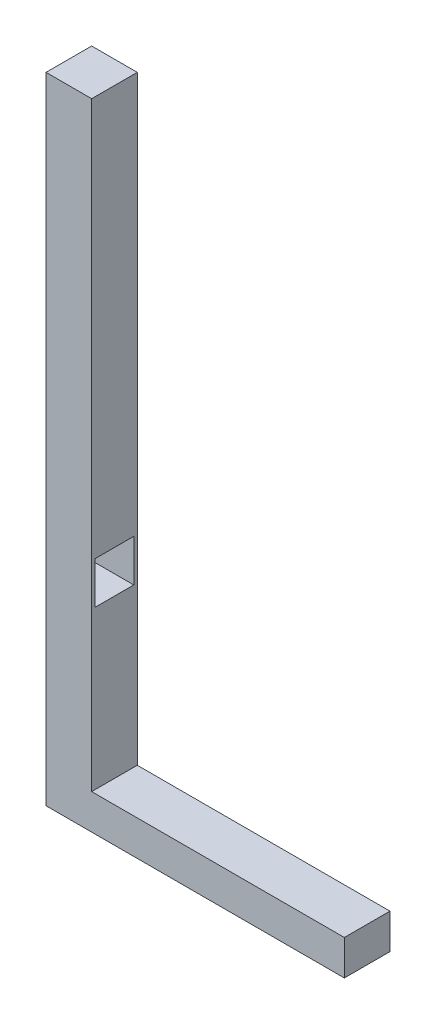
SolidWorks part; units mm, degrees
ref_plane "Plan de face" through (0, 0, 0) normal (0, 0, 1) x (1, 0, 0)
ref_plane "Plan de dessus" through (0, 0, 0) normal (0, 1, 0) x (1, 0, 0)
ref_plane "Plan de droite" through (0, 0, 0) normal (1, 0, 0) x (0, 0, -1)
sketch "Esquisse2" plane through (0, 0, 0) normal (0, 0, 1) x (1, 0, 0)
  line L1 (-71.3354, 181) -> (-58.3354, 181)
  line L2 (-71.3354, 181) -> (-71.3354, 10)
  line L3 (-71.3354, 10) -> (-58.3354, 10)
  line L4 (-58.3354, 181) -> (-58.3354, 10)
  line L5 (-71.3354, 10) -> (13.6646, 10)
  line L6 (-71.3354, 10) -> (-71.3354, 0)
  line L7 (-71.3354, 0) -> (13.6646, 0)
  line L8 (13.6646, 10) -> (13.6646, 0)
  dimension "D1" = 13
  dimension "D2" = 171
  dimension "D3" = 10
  dimension "D4" = 85
extrude "Boss.-Extru.1" add sketch "Esquisse2" along normal blind 13 contours L2 L1 L4 L3
extrude "Boss.-Extru.2" add sketch "Esquisse2<3>" along normal blind 13 contours L8 L5 L3 L6 L7 region at (-28.8354, 5, 0)
sketch "Esquisse2<3>" plane through (0, 0, 0) normal (0, 0, 1) x (1, 0, 0) same geometry as "Esquisse2"
ref_plane "Plan1" through (-58.3354, 10, 13) normal (0, -1, 0) x (-1, 0, 0)
sketch "Esquisse4" plane through (-58.3354, 0, 0) normal (1, 0, 0) x (0, 0, -1)
  line L1 (0, 181) -> (0, 10) construction
  line L2 (-12, 67) -> (-1, 67)
  line L3 (-12, 67) -> (-12, 55)
  line L4 (-12, 55) -> (-1, 55)
  line L5 (-1, 67) -> (-1, 55)
  line L6 (-13, 181) -> (0, 181) construction
  dimension "D1" = 11
  dimension "D2" = 12
  dimension "D3" = 1
  dimension "D4" = 114
extrude "Enlèv. mat.-Extru.2" cut sketch "Esquisse4" against normal blind 37
